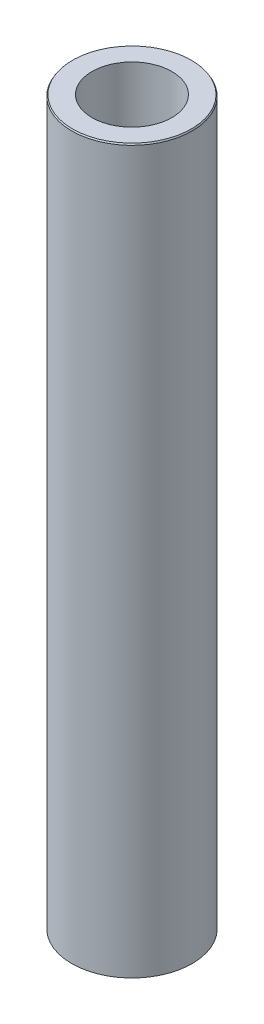
SolidWorks part; units mm, degrees
ref_plane "Front Plane" through (0, 0, 0) normal (0, 0, 1) x (1, 0, 0)
ref_plane "Top Plane" through (0, 0, 0) normal (0, 1, 0) x (1, 0, 0)
ref_plane "Right Plane" through (0, 0, 0) normal (1, 0, 0) x (0, 0, -1)
sketch "Sketch1" plane through (0, 0, 0) normal (0, 1, 0) x (1, 0, 0)
  circle A0 centre (0, 0) radius 50
  dimension "SHAFT_OD" = 100
extrude "Boss-Extrude1" add sketch "Sketch1" along normal blind 600
sketch "Sketch2" plane through (0, 0, 0) normal (0, 1, 0) x (1, 0, 0)
  circle A0 centre (0, 0) radius 33.1479
  dimension "BORE_D" = 66.2958
extrude "Cut-Extrude1" cut sketch "Sketch2" along normal through all
chamfer "Chamfer1" distance 1.1434 angle 30 2 edges at (0, 600, 50) (0, 0, 50) first distance on face at (0, 600, 50) first distance on face at (0, 0, 33.1479)
